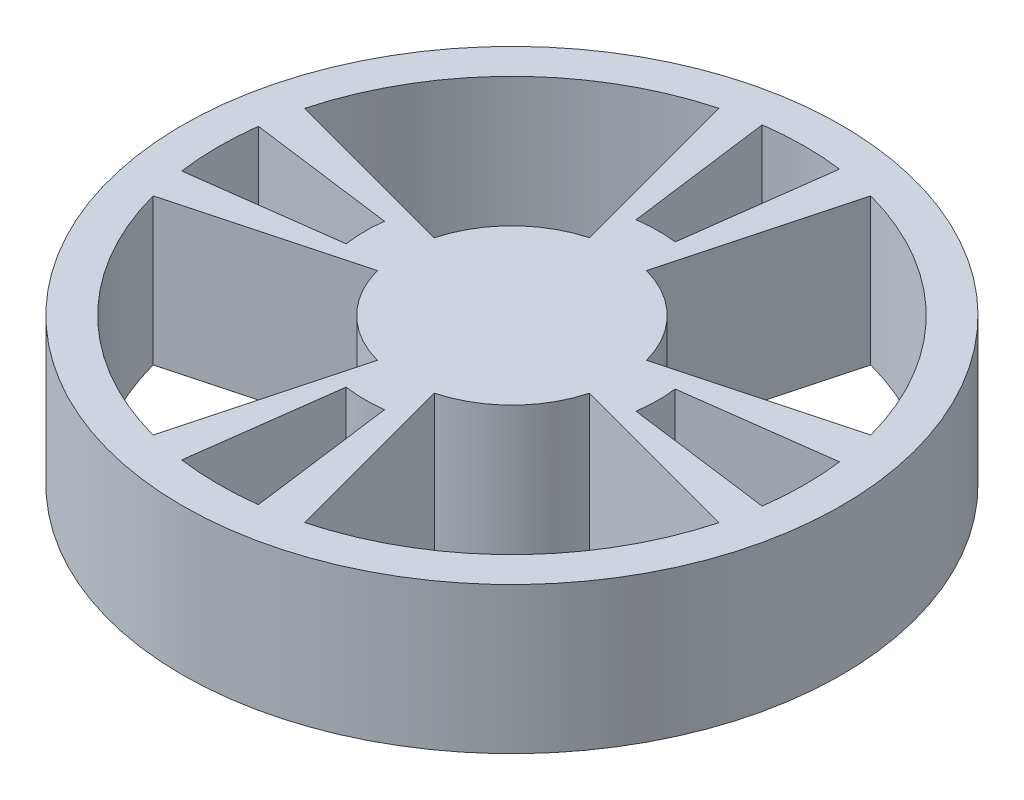
SolidWorks part; units mm, degrees
ref_plane "Front Plane" through (0, 0, 0) normal (0, 0, 1) x (1, 0, 0)
ref_plane "Top Plane" through (0, 0, 0) normal (0, 1, 0) x (1, 0, 0)
ref_plane "Right Plane" through (0, 0, 0) normal (1, 0, 0) x (0, 0, -1)
sketch "Sketch1" plane through (0, 0, 0) normal (0, 1, 0) x (1, 0, 0)
  circle A0 centre (0, 0) radius 9.525
  dimension "D1" = 19.05
extrude "Boss-Extrude1" add sketch "Sketch1" along normal blind 2.54
sketch "Sketch3" plane through (0, 2.54, 0) normal (0, 1, 0) x (1, 0, 0)
  line L0 (0, 0) -> (28.575, 0) construction
  line L1 (0, 0) -> (0, 28.575) construction
  line L2 (0, 0) -> (27.6013, 7.3958) construction
  line L3 (-2.4653, 9.2004) -> (-6.574, 24.5345)
  line L4 (9.2004, 2.4653) -> (24.5345, 6.574)
  line L5 (-9.2004, 2.4653) -> (-24.5345, 6.574)
  line L6 (0, 0) -> (20.2056, 20.2056) construction
  line L8 (2.4653, 9.2004) -> (6.574, 24.5345)
  line L9 (9.2004, -2.4653) -> (24.5345, -6.574)
  line L10 (2.4653, -9.2004) -> (6.574, -24.5345)
  line L11 (-9.2004, -2.4653) -> (-24.5345, -6.574)
  line L12 (-2.4653, -9.2004) -> (-6.574, -24.5345)
  circle A0 centre (0, 0) radius 28.575
  circle A2 centre (0, 0) radius 25.4 construction
  circle A3 centre (0, 0) radius 9.525 construction
  arc A4 (-9.2004, 2.4653) -> (-2.4653, 9.2004) centre (0, 0) cw
  arc A5 (9.2004, 2.4653) -> (2.4653, 9.2004) centre (0, 0) ccw
  arc A8 (24.5345, 6.574) -> (6.574, 24.5345) centre (0, 0) ccw
  arc A9 (-24.5345, 6.574) -> (-6.574, 24.5345) centre (0, 0) cw
  arc A10 (9.2004, -2.4653) -> (2.4653, -9.2004) centre (0, 0) cw
  arc A11 (24.5345, -6.574) -> (6.574, -24.5345) centre (0, 0) cw
  arc A12 (-24.5345, -6.574) -> (-6.574, -24.5345) centre (0, 0) ccw
  arc A13 (-9.2004, -2.4653) -> (-2.4653, -9.2004) centre (0, 0) ccw
  dimension "D1" = 57.15
  dimension "D2" = 15
  dimension "D4" = 3.175
  dimension "D3" = 45
extrude "Boss-Extrude2" add sketch "Sketch3" along normal blind 12.7
sketch "Sketch4" plane through (0, 15.24, 0) normal (0, 1, 0) x (1, 0, 0)
  line L0 (0, 0) -> (28.575, 0) construction
  line L1 (0, 0) -> (0, 28.575) construction
  line L2 (12.6046, 1.5541) -> (25.1961, 3.2118)
  line L5 (12.5705, -1.8088) -> (25.1623, -3.4665)
  line L6 (-12.6046, 1.5541) -> (-25.1961, 3.2118)
  line L7 (-12.5705, -1.8088) -> (-25.1623, -3.4665)
  line L8 (0, 0) -> (20.2056, 20.2056) construction
  line L9 (1.5541, 12.6046) -> (3.2118, 25.1961)
  line L10 (-1.8088, 12.5705) -> (-3.4665, 25.1623)
  line L11 (-1.8088, -12.5705) -> (-3.4665, -25.1623)
  line L12 (1.5541, -12.6046) -> (3.2118, -25.1961)
  circle A2 centre (0, 0) radius 12.7 construction
  arc A3 (-2.4653, 9.2004) -> (-9.2004, 2.4653) centre (0, 0) ccw construction
  circle A4 centre (0, 0) radius 25.4 construction
  arc A5 (12.5705, -1.8088) -> (12.6046, 1.5541) centre (0, 0) ccw
  arc A6 (-6.574, 24.5345) -> (-24.5345, 6.574) centre (0, 0) ccw construction
  circle A7 centre (0, 0) radius 28.575 construction
  arc A8 (25.1623, -3.4665) -> (25.1961, 3.2118) centre (0, 0) ccw
  arc A9 (-12.5705, -1.8088) -> (-12.6046, 1.5541) centre (0, 0) cw
  arc A10 (-25.1623, -3.4665) -> (-25.1961, 3.2118) centre (0, 0) cw
  arc A11 (-1.8088, 12.5705) -> (1.5541, 12.6046) centre (0, 0) cw
  arc A12 (-3.4665, 25.1623) -> (3.2118, 25.1961) centre (0, 0) cw
  arc A13 (-3.4665, -25.1623) -> (3.2118, -25.1961) centre (0, 0) ccw
  arc A14 (-1.8088, -12.5705) -> (1.5541, -12.6046) centre (0, 0) ccw
  dimension "D1" = 3.175
  dimension "D2" = 0
  dimension "D3" = 7.5
  dimension "D4" = 7.5
  dimension "D5" = 45
extrude "Cut-Extrude2" cut sketch "Sketch4" against normal through all
sketch "Sketch2" plane through (0, 0, 0) normal (0, 1, 0) x (1, 0, 0)
  line L1 (-4.5529, 1.8859) -> (-1.8859, 4.5529)
  line L2 (-2.667, 2.667) -> (2.667, -2.667) construction
  line L3 (0, 2.667) -> (-1.8859, 4.5529)
  line L4 (1.8859, 4.5529) -> (4.5529, 1.8859)
  line L5 (0, 2.667) -> (1.8859, 4.5529)
  line L6 (0, -2.667) -> (1.8859, -4.5529)
  line L7 (-4.5529, -1.8859) -> (-1.8859, -4.5529)
  line L8 (-2.667, 0) -> (-4.5529, 1.8859)
  line L9 (1.8859, -4.5529) -> (4.5529, -1.8859)
  line L10 (-2.667, -2.667) -> (2.667, -2.667) construction
  line L11 (-2.667, 0) -> (-4.5529, -1.8859)
  line L12 (2.667, 0) -> (4.5529, 1.8859)
  line L13 (-2.667, 2.667) -> (2.667, 2.667) construction
  line L14 (2.667, 0) -> (4.5529, -1.8859)
  line L15 (2.667, -2.667) -> (2.667, 2.667) construction
  line L16 (-2.667, -2.667) -> (-2.667, 2.667) construction
  line L17 (0, -2.667) -> (-1.8859, -4.5529)
  line L18 (-2.667, -2.667) -> (2.667, 2.667) construction
  point P23 (-2.667, 0)
  dimension "D1" = 3.7717
  dimension "D2" = 2.667
  dimension "D3" = 2.667
  dimension "D4" = 3.7717
  dimension "D5" = 2.667
  dimension "D6" = 2.667
  dimension "D7" = 3.7717
  dimension "D8" = 2.667
  dimension "D9" = 2.667
  dimension "D10" = 3.7717
  dimension "D11" = 2.667
  dimension "D12" = 2.667
  dimension "D13" = 5.334
  dimension "D14" = 5.334
  dimension "D15" = 3.7717
extrude "Cut-Extrude3" cut sketch "Sketch2" along normal blind 8.4667
